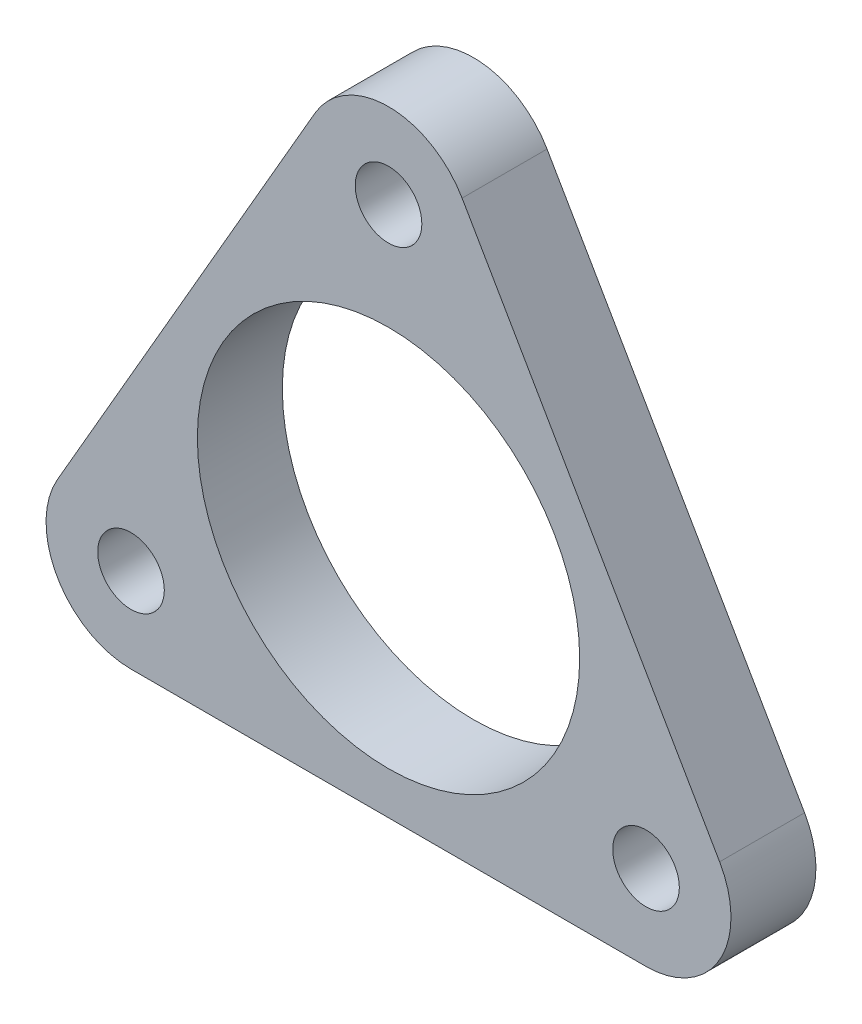
SolidWorks part; units mm, degrees
material "6061-T6 (SS)"
ref_plane "Front Plane" through (0, 0, 0) normal (0, 0, 1) x (1, 0, 0)
ref_plane "Top Plane" through (0, 0, 0) normal (0, 1, 0) x (1, 0, 0)
ref_plane "Right Plane" through (0, 0, 0) normal (1, 0, 0) x (0, 0, -1)
sketch "Sketch2" plane through (0, 0, 0) normal (0, 0, 1) x (1, 0, 0)
  line L0 (0, 34.925) -> (30.2459, -17.4625)
  line L1 (30.2459, -17.4625) -> (-30.2459, -17.4625)
  line L2 (-30.2459, -17.4625) -> (0, 34.925)
  circle A0 centre (0, 0) radius 14.2875
  circle A1 centre (0, 22.225) radius 2.4892
  circle A2 centre (19.2474, -11.1125) radius 2.4892
  circle A3 centre (-19.2474, -11.1125) radius 2.4892
  circle A4 centre (19.2474, -11.1125) radius 6.35 construction
  point P11 (0, 0)
  point P16 (0, -17.4625)
  dimension "D1" = 28.575
  dimension "D2" = 4.9784
  dimension "D6" = 12.7
  dimension "D3" = 22.225
  dimension "D4" = 3
extrude "Boss-Extrude1" add sketch "Sketch2" along normal blind 6.35
fillet "Fillet1" radius 6.35 3 edges at (30.2459, -17.4625, 3.175) (-30.2459, -17.4625, 3.175) (0, 34.925, 3.175)
